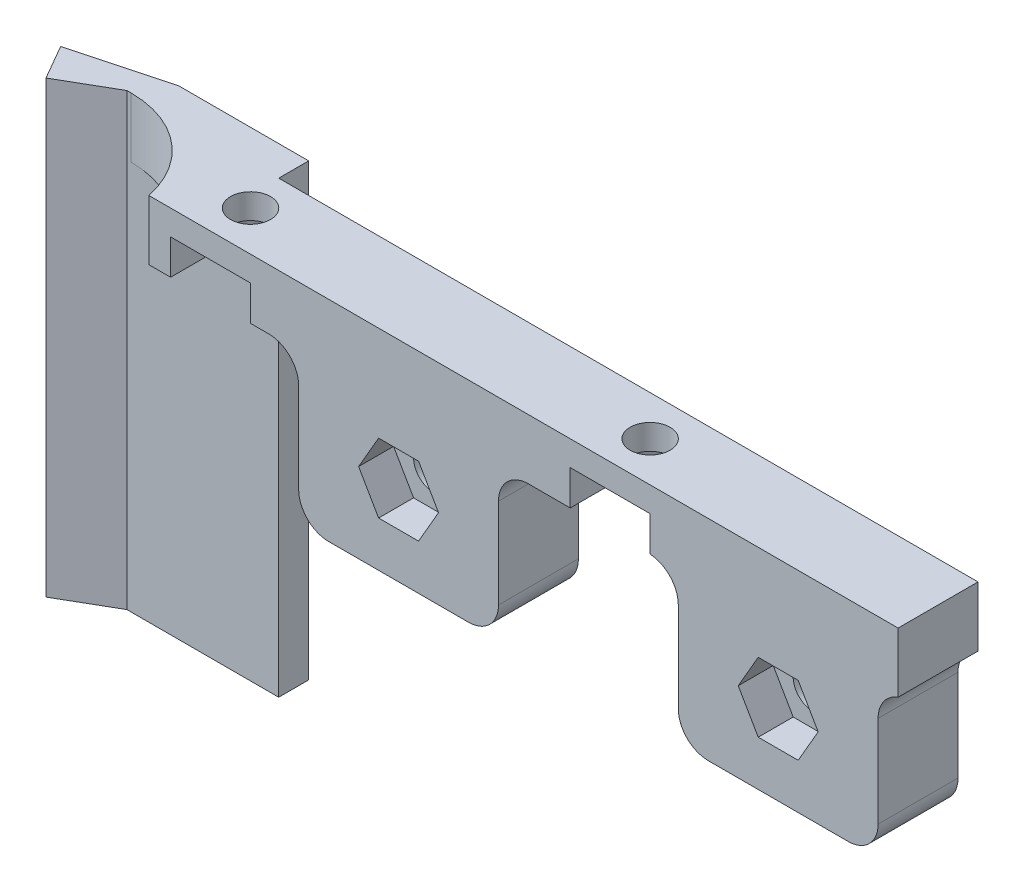
SolidWorks part; units mm, degrees
ref_plane "Plan de face" through (0, 0, 0) normal (0, 0, 1) x (1, 0, 0)
ref_plane "Plan de dessus" through (0, 0, 0) normal (0, 1, 0) x (1, 0, 0)
ref_plane "Plan de droite" through (0, 0, 0) normal (1, 0, 0) x (0, 0, -1)
sketch "Esquisse1" plane through (0, 0, 0) normal (0, 1, 0) x (1, 0, 0)
  line L0 (-13.6651, 0.5) -> (-11.6651, -2.9641)
  line L1 (-11.6651, -2.9641) -> (-6.5311, 0)
  line L2 (-13.6651, 0.5) -> (-4.3349, 3)
  line L3 (-4.3349, 3) -> (8.6651, 3)
  line L4 (8.6651, 3) -> (8.6651, 0)
  line L5 (8.6651, 0) -> (78.6651, 0)
  line L6 (78.6651, 0) -> (78.6651, -8)
  line L7 (78.6651, -8) -> (3.6651, -8)
  line L8 (3.6651, -8) -> (3.6651, 0)
  line L9 (3.6651, 0) -> (-6.5311, 0)
  circle A0 centre (49.8446, -4) radius 2
  circle A1 centre (9.8446, -4) radius 2
  circle A2 centre (9.8446, -4) radius 2 construction
  point P2 (3.6651, -4)
  point P8 (8.6651, 1.5)
  point P12 (43.6651, 0)
  dimension "D1" = 3
  dimension "D2" = 5
  dimension "D3" = 8
  dimension "D4" = 13
  dimension "D5" = 70
  dimension "D7" = 150
  dimension "D8" = 165
  dimension "D9" = 4
  dimension "D10" = 5.134
extrude "Boss.-Extru.1" add sketch "Esquisse1" along normal blind 45
sketch "Esquisse2" plane through (0, 0, 8) normal (0, 0, 1) x (1, 0, 0)
  line L0 (3.6651, 45) -> (78.6651, 45) construction
  line L1 (78.6651, 0) -> (3.6651, 0)
  line L2 (78.6651, 0) -> (78.6651, 39)
  line L3 (78.6651, 39) -> (3.6651, 39)
  line L4 (3.6651, 0) -> (3.6651, 39)
  line L5 (78.6651, 0) -> (3.6651, 39) construction
  line L6 (78.6651, 39) -> (3.6651, 0) construction
  line L8 (3.6651, 45) -> (3.6651, 0) construction
  point P4 (41.1651, 19.5)
  dimension "D1" = 6
extrude "Enlèv. mat.-Extru.1" cut sketch "Esquisse2" against normal up to surface (8 mm away) up to face at (43.6651, 22.5, 0)
sketch "Esquisse3" plane through (0, 39, 0) normal (0, -1, 0) x (1, 0, 0)
  line L0 (51.8446, 0.5359) -> (47.8446, 0.5359)
  line L1 (47.8446, 0.5359) -> (45.8446, 4)
  line L2 (51.8446, 7.4641) -> (53.8446, 4) construction
  line L3 (47.8446, 7.4641) -> (51.8446, 7.4641) construction
  line L4 (47.8446, 7.4641) -> (45.8446, 4) construction
  line L5 (53.8446, 4) -> (51.8446, 0.5359)
  line L6 (51.8446, 0.5359) -> (47.8446, 7.4641) construction
  line L7 (47.8446, 0.5359) -> (51.8446, 7.4641) construction
  line L8 (53.8446, 4) -> (53.8446, 8)
  line L9 (45.8446, 4) -> (45.8446, 8)
  line L10 (45.8446, 8) -> (53.8446, 8)
  line L11 (78.6651, 8) -> (3.6651, 8) construction
  line L12 (11.8446, 0.5359) -> (7.8446, 0.5359)
  line L13 (7.8446, 0.5359) -> (5.8446, 4)
  line L14 (11.8446, 7.4641) -> (13.8446, 4) construction
  line L15 (7.8446, 7.4641) -> (11.8446, 7.4641) construction
  line L16 (7.8446, 7.4641) -> (5.8446, 4) construction
  line L17 (13.8446, 4) -> (11.8446, 0.5359)
  line L18 (11.8446, 0.5359) -> (7.8446, 7.4641) construction
  line L19 (7.8446, 0.5359) -> (11.8446, 7.4641) construction
  line L20 (13.8446, 4) -> (13.8446, 8)
  line L21 (5.8446, 4) -> (5.8446, 8)
  line L22 (5.8446, 8) -> (13.8446, 8)
  circle A0 centre (49.8446, 4) radius 3.4641 construction
  circle A1 centre (9.8446, 4) radius 3.4641 construction
  point P10 (49.8446, 4)
  point P12 (45.3446, -3.5788)
  point P13 (0, 0)
  point P14 (45.3446, -3.3515)
  point P15 (55.2136, -2.2509)
  point P16 (45.3446, -2.5511)
  point P17 (54.013, -4.7315)
  point P18 (45.3446, -4.919)
  point P19 (43.6408, -7.5537)
  point P20 (0, 0)
  point P21 (64.9229, -4.7621)
  point P22 (54.7603, 21.9569)
  point P23 (54.3446, 9.7882)
  point P36 (9.8446, 4)
  dimension "D1" = 4
  dimension "D2" = 4
extrude "Enlèv. mat.-Extru.2" cut sketch "Esquisse3" against normal blind 3.5
fillet "Congé1" radius 10 1 edges at (3.6651, 42, 0)
sketch "Esquisse4" plane through (0, 39, 0) normal (0, -1, 0) x (1, 0, 0)
  line L0 (45.8446, 8) -> (13.8446, 8) construction
  line L1 (18.6651, 8) -> (38.6651, 8)
  line L2 (18.6651, 8) -> (18.6651, 0)
  line L3 (18.6651, 0) -> (38.6651, 0)
  line L4 (38.6651, 8) -> (38.6651, 0)
  line L5 (18.6651, 8) -> (38.6651, 0) construction
  line L6 (18.6651, 0) -> (38.6651, 8) construction
  line L7 (8.6651, 0) -> (78.6651, 0) construction
  line L8 (78.6651, 8) -> (53.8446, 8) construction
  line L9 (56.6651, 8) -> (76.6651, 8)
  line L10 (56.6651, 8) -> (56.6651, 0)
  line L11 (56.6651, 0) -> (76.6651, 0)
  line L12 (76.6651, 8) -> (76.6651, 0)
  line L13 (56.6651, 8) -> (76.6651, 0) construction
  line L14 (56.6651, 0) -> (76.6651, 8) construction
  line L16 (78.6651, 0) -> (78.6651, 8) construction
  point P4 (28.6651, 4)
  point P13 (66.6651, 4)
  point P16 (75.2274, 0)
  point P18 (0, 0)
  point P20 (33.6651, 4)
  point P21 (43.6651, 0)
  point P22 (0, 0)
  point P23 (39.511, 0)
  point P24 (0, 0)
  point P25 (78.6651, 4)
  point P26 (0, 0)
  dimension "D1" = 20
  dimension "D2" = 20
  dimension "D3" = 2
  dimension "D4" = 40
extrude "Boss.-Extru.2" add sketch "Esquisse4" along normal blind 15
fillet "Congé3" radius 3 8 edges at (18.6651, 39, 4) (38.6651, 39, 4) (76.6651, 39, 4) (56.6651, 39, 4) (76.6651, 24, 4) (56.6651, 24, 4) (38.6651, 24, 4) (18.6651, 24, 4)
sketch "Esquisse5" plane through (0, 0, 8) normal (0, 0, 1) x (1, 0, 0)
  line L0 (28.6651, 24) -> (28.6651, 47.6442) construction
  line L1 (35.6651, 24) -> (21.6651, 24) construction
  line L2 (66.6651, 24) -> (66.6651, 54.774) construction
  line L3 (73.6651, 24) -> (59.6651, 24) construction
  line L4 (14.438, 32) -> (89.633, 32) construction
  line L5 (30.6651, 28.5359) -> (26.6651, 28.5359)
  line L6 (26.6651, 28.5359) -> (24.6651, 32)
  line L7 (30.6651, 35.4641) -> (32.6651, 32)
  line L8 (26.6651, 35.4641) -> (30.6651, 35.4641)
  line L9 (26.6651, 35.4641) -> (24.6651, 32)
  line L10 (32.6651, 32) -> (30.6651, 28.5359)
  line L11 (30.6651, 28.5359) -> (26.6651, 35.4641) construction
  line L12 (26.6651, 28.5359) -> (30.6651, 35.4641) construction
  line L13 (32.6651, 32) -> (32.6741, 32)
  line L14 (68.6651, 28.5359) -> (64.6651, 28.5359)
  line L15 (64.6651, 28.5359) -> (62.6651, 32)
  line L16 (68.6651, 35.4641) -> (70.6651, 32)
  line L17 (64.6651, 35.4641) -> (68.6651, 35.4641)
  line L18 (64.6651, 35.4641) -> (62.6651, 32)
  line L19 (70.6651, 32) -> (68.6651, 28.5359)
  line L20 (68.6651, 28.5359) -> (64.6651, 35.4641) construction
  line L21 (64.6651, 28.5359) -> (68.6651, 35.4641) construction
  line L22 (70.6651, 32) -> (70.6741, 32)
  circle A0 centre (28.6651, 32) radius 3.4641 construction
  circle A1 centre (66.6651, 32) radius 3.4641 construction
  point P10 (28.6651, 32)
  point P11 (66.6651, 32)
  point P21 (66.6651, 32)
  point P22 (28.6651, 32)
  point P32 (0, 0)
  dimension "D1" = 8
  dimension "D2" = 4
  dimension "D3" = 4
extrude "Enlèv. mat.-Extru.3" cut sketch "Esquisse5" against normal blind 3.5 contours L10 L7 L8 L9 L6 L5 | L19 L16 L17 L18 L15 L14 region at (28.6651, 32, 8) region at (66.6651, 32, 8)
sketch "Esquisse6" plane through (0, 0, 4.5) normal (0, 0, 1) x (1, 0, 0)
  line L0 (26.6651, 35.4641) -> (30.6651, 28.5359) construction
  line L1 (26.6651, 28.5359) -> (30.6651, 35.4641) construction
  line L2 (30.6651, 35.4641) -> (32.6651, 32) construction
  line L3 (30.6651, 35.4641) -> (32.6651, 32) construction
  line L4 (64.6651, 35.4641) -> (68.6651, 28.5359) construction
  line L5 (64.6651, 28.5359) -> (68.6651, 35.4641) construction
  line L6 (64.6651, 35.4641) -> (62.6651, 32) construction
  line L7 (64.6651, 35.4641) -> (62.6651, 32) construction
  circle A0 centre (28.6651, 32) radius 2
  circle A1 centre (66.6651, 32) radius 2
  point P11 (28.6651, 32)
  point P16 (66.6651, 32)
  dimension "D1" = 4
extrude "Enlèv. mat.-Extru.4" cut sketch "Esquisse6" against normal through all
